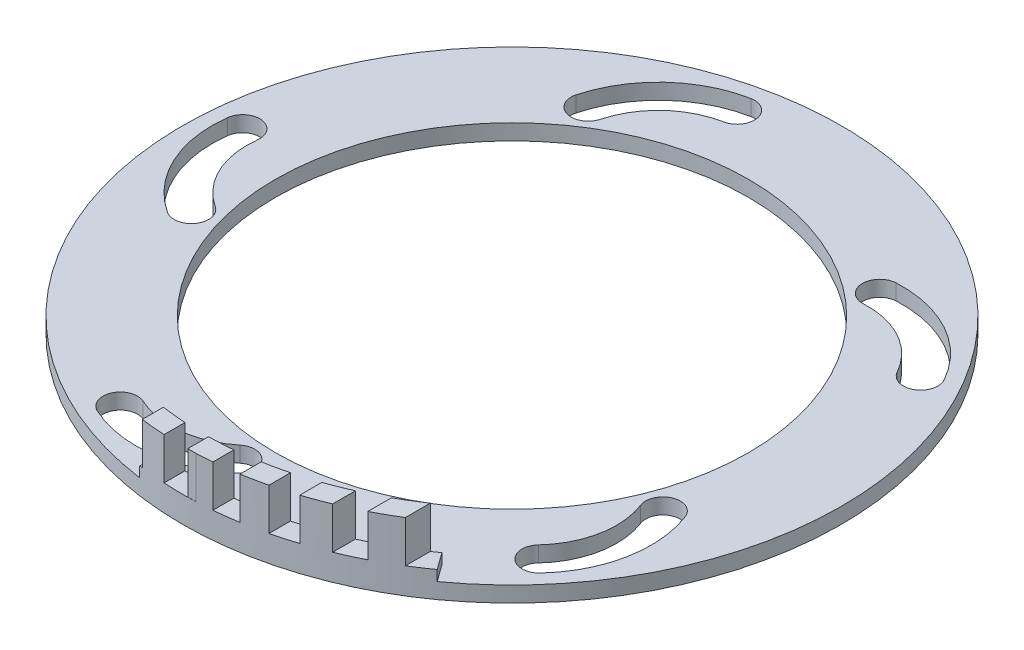
SolidWorks part; units mm, degrees
ref_plane "Front Plane" through (0, 0, 0) normal (0, 0, 1) x (1, 0, 0)
ref_plane "Top Plane" through (0, 0, 0) normal (0, 1, 0) x (1, 0, 0)
ref_plane "Right Plane" through (0, 0, 0) normal (1, 0, 0) x (0, 0, -1)
sketch "Sketch1" plane through (0, 0, 0) normal (0, 1, 0) x (1, 0, 0)
  line L0 (0, -47.6814) -> (0, 53.28) construction
  line L1 (-42.487, -16.8128) -> (53.5331, 14.386) construction
  line L2 (-26.2584, 33.1337) -> (33.0853, -48.5459) construction
  line L3 (26.2584, 33.1337) -> (-33.0853, -48.5459) construction
  line L4 (42.487, -16.8128) -> (-53.5331, 14.386) construction
  line L5 (0, -3.008) -> (0, -47.6814) construction
  circle A0 centre (0, 0) radius 31.5
  circle A1 centre (0, 0) radius 22.625
  arc A2 (-15.2424, 21.3741) -> (-6.5856, 29.4237) centre (-4.477, 18.4762) cw
  arc A3 (-12.0559, 20.5163) -> (-5.9614, 26.1832) centre (-4.477, 18.4762) cw
  arc A4 (-15.2424, 21.3741) -> (-12.0559, 20.5163) centre (-13.6491, 20.9452) ccw
  arc A5 (-6.5856, 29.4237) -> (-5.9614, 26.1832) centre (-6.2735, 27.8034) cw
  arc A6 (15.7867, 17.8057) -> (23.0595, 13.7607) centre (16.1885, 9.9673) cw
  arc A7 (15.6178, 21.1014) -> (25.9485, 15.3557) centre (16.1885, 9.9673) cw
  arc A8 (15.6178, 21.1014) -> (15.7867, 17.8057) centre (15.7022, 19.4535) ccw
  arc A9 (25.9485, 15.3557) -> (23.0595, 13.7607) centre (24.504, 14.5582) cw
  arc A10 (21.8126, -9.5118) -> (20.213, -17.6786) centre (14.482, -12.3161) cw
  arc A11 (24.8947, -8.3327) -> (22.6226, -19.9333) centre (14.482, -12.3161) cw
  arc A12 (24.8947, -8.3327) -> (21.8126, -9.5118) centre (23.3537, -8.9222) ccw
  arc A13 (22.6226, -19.9333) -> (20.213, -17.6786) centre (21.4178, -18.806) cw
  arc A14 (-2.3058, -23.6843) -> (-10.5672, -24.6867) centre (-7.2381, -17.5791) cw
  arc A15 (-0.232, -26.2513) -> (-11.9669, -27.6752) centre (-7.2381, -17.5791) cw
  arc A16 (-0.232, -26.2513) -> (-2.3058, -23.6843) centre (-1.2689, -24.9678) ccw
  arc A17 (-11.9669, -27.6752) -> (-10.5672, -24.6867) centre (-11.2671, -26.1809) cw
  arc A18 (-23.2376, -5.1259) -> (-26.7439, 2.4214) centre (-18.9554, 1.4516) cw
  arc A19 (-25.0381, -7.8915) -> (-30.0186, 2.8292) centre (-18.9554, 1.4516) cw
  arc A20 (-25.0381, -7.8915) -> (-23.2376, -5.1259) centre (-24.1379, -6.5087) ccw
  arc A21 (-30.0186, 2.8292) -> (-26.7439, 2.4214) centre (-28.3813, 2.6253) cw
  point P4 (0, 24.1)
  point P59 (0, 0)
  dimension "D1" = 63
  dimension "D2" = 45.25
  dimension "D3" = 24.1
  dimension "D4" = 5
  dimension "D5" = 44.6735
  dimension "D6" = 28.5024
  dimension "D8" = 3.3
  dimension "D10" = 11.1487
  dimension "D11" = 25
  dimension "D7" = 2
  dimension "D9" = 29.4237
  dimension "D12" = 5
extrude "Boss-Extrude1" add sketch "Sketch1" along normal blind 1.5 contours A0 A1 A2 A5 A3 A4 region at (-30.609, 0, 0)
sketch "Sketch2" plane through (0, 1.5, 0) normal (0, 1, 0) x (1, 0, 0)
  line L2 (-4.1115, -29.2121) -> (-4.3902, -31.1926)
  line L3 (17.2419, -23.9367) -> (18.4109, -25.5595)
  circle A0 centre (0, 0) radius 31.5 construction
  arc A1 (18.4109, -25.5595) -> (-4.3902, -31.1926) centre (0, 0) cw
  arc A3 (17.2419, -23.9367) -> (-4.1115, -29.2121) centre (0, 0) cw
  point P0 (-2.584, -26.9765)
  point P1 (16.0281, -21.852)
  dimension "D1" = 27.1
  dimension "D2" = 27.1
  dimension "D3" = 2
extrude "Boss-Extrude2" add sketch "Sketch2" along normal blind 5
sketch "Sketch5" plane through (0, 6.5, 0) normal (0, 1, 0) x (1, 0, 0)
  line L1 (-4.1115, -29.2121) -> (-1.8115, -29.2121)
  line L2 (-4.1115, -29.2121) -> (-4.1115, -31.4479)
  line L3 (-4.1115, -31.4479) -> (-1.8115, -31.4479)
  line L4 (-1.8115, -29.2121) -> (-1.8115, -31.4479)
  line L9 (0.4885, -25.4743) -> (2.7885, -25.4743)
  line L10 (0.4885, -25.4743) -> (0.4885, -31.4743)
  line L11 (0.4885, -31.4743) -> (2.7885, -31.4743)
  line L12 (2.7885, -25.4743) -> (2.7885, -31.4743)
  line L13 (5.0885, -25.4743) -> (7.3885, -25.4743)
  line L14 (5.0885, -25.4743) -> (5.0885, -31.4743)
  line L15 (5.0885, -31.4743) -> (7.3885, -31.4743)
  line L16 (7.3885, -25.4743) -> (7.3885, -31.4743)
  line L17 (9.6885, -23.7189) -> (11.9885, -23.7189)
  line L18 (9.6885, -23.7189) -> (9.6885, -32.7858)
  line L19 (9.6885, -32.7858) -> (11.9885, -32.7858)
  line L20 (11.9885, -23.7189) -> (11.9885, -32.7858)
  line L21 (14.2885, -22.6296) -> (16.5885, -22.6296)
  line L22 (14.2885, -22.6296) -> (14.2885, -31.156)
  line L23 (14.2885, -31.156) -> (16.5885, -31.156)
  line L24 (16.5885, -22.6296) -> (16.5885, -31.156)
  arc A0 (-4.3902, -31.1926) -> (18.4109, -25.5595) centre (0, 0) ccw construction
  dimension "D1" = 2.3
  dimension "D2" = 2.3
  dimension "D3" = 2.3
  dimension "D4" = 6
  dimension "D5" = 2.3
  dimension "D6" = 2.3
  dimension "D7" = 6
  dimension "D8" = 2.3
  dimension "D9" = 2.3
  dimension "D10" = 2.3
  dimension "D11" = 2.3
extrude "Cut-Extrude10" cut sketch "Sketch5" against normal blind 4 flip side to cut
